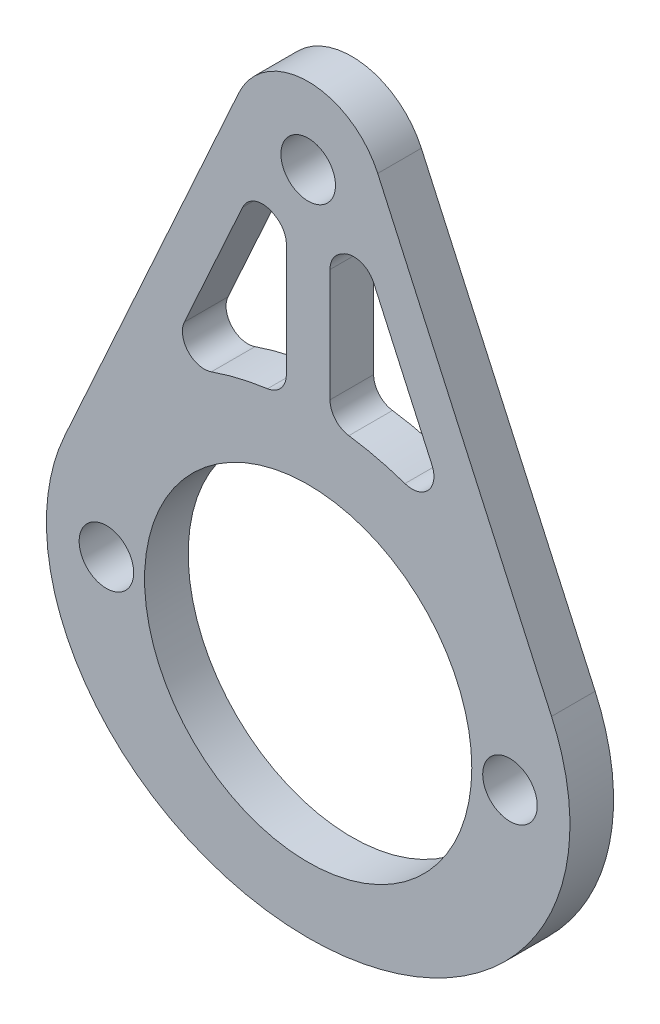
SolidWorks part; units mm, degrees
material "2018 合金"
ref_plane "正面" through (0, 0, 0) normal (0, 0, 1) x (1, 0, 0)
ref_plane "平面" through (0, 0, 0) normal (0, 1, 0) x (1, 0, 0)
ref_plane "右側面" through (0, 0, 0) normal (1, 0, 0) x (0, 0, -1)
sketch "ｽｹｯﾁ1" plane through (0, 0, 0) normal (0, 0, 1) x (1, 0, 0)
  line L0 (0, 0) -> (9.25, 0) construction
  line L1 (0, 0) -> (0, 7.5) construction
  line L2 (0, 0) -> (0, 20) construction
  line L3 (-11.1545, 3.8716) -> (-3.1877, 21.4451)
  line L4 (11.1545, 3.8716) -> (3.1877, 21.4451)
  circle A0 centre (0, 0) radius 7.5
  circle A1 centre (9.25, 0) radius 2.75 construction
  circle A2 centre (9.25, 0) radius 1
  circle A3 centre (0, 0) radius 10.5 construction
  circle A4 centre (-9.25, 0) radius 1
  circle A5 centre (0, 20) radius 3 construction
  arc A6 (3.1877, 21.4451) -> (-3.1877, 21.4451) centre (0, 20) ccw
  ellipse E0 centre (0, 0) end of major axis (12, 0) minor radius 10.5 (-11.1545, 3.8716) -> (11.1545, 3.8716) ccw
  dimension "D1" = 18.5
  dimension "D2" = 15
  dimension "D3" = 5.5
  dimension "D4" = 2
  dimension "D7" = 6
  dimension "D8" = 0.5
  dimension "D6" = 20
  dimension "D5" = 3
extrude "ﾎﾞｽ - 押し出し1" add sketch "ｽｹｯﾁ1" along normal blind 2
hole_wizard "M3 ねじ穴1" positions "ｽｹｯﾁ2" profile "ｽｹｯﾁ3" tap size "M3" standard "JIS" end condition through all
sketch "ｽｹｯﾁ2" plane through (0, 0, 0) normal (0, 0, -1) x (-1, 0, 0)
  point P0 (-9.25, 0)
  point P3 (9.25, 0)
sketch "ｽｹｯﾁ3" plane through (9.25, 0, 0) normal (1, 0, 0) x (0, 1, 0)
  line L0 (0, 0) -> (0, 2)
  line L1 (0, 2) -> (1.25, 2)
  line L2 (1.25, 2) -> (1.25, 0)
  line L5 (1.25, 0) -> (0, 0)
  line L11 (0, -6.35) -> (0, 107.95) construction
  dimension "次ｻｰﾌｪｽまでのねじ下穴ﾄﾞﾘﾙ直径" = 2.5
  dimension "次ｻｰﾌｪｽまでのねじ下穴ﾄﾞﾘﾙの深さ" = 2
cosmetic thread "穴のねじ山1" parameters "D2"=3
cosmetic thread "穴のねじ山2" parameters "D2"=3
sketch "ｽｹｯﾁ4" plane through (0, 0, 0) normal (0, 0, -1) x (-1, 0, 0)
  line L0 (0, 20) -> (0, 0) construction
  line L2 (1, 10.4635) -> (-1, 10.4635)
  line L3 (1, 10.4635) -> (1, 17.1716)
  line L4 (1, 17.1716) -> (-1, 17.1716)
  line L5 (-1, 10.4635) -> (-1, 17.1716)
  line L6 (1, 10.4635) -> (-1, 17.1716) construction
  line L7 (1, 17.1716) -> (-1, 10.4635) construction
  line L9 (1.3662, 20.6193) -> (9.3329, 3.0458)
  line L10 (1.3662, 20.6193) -> (9.3329, 3.0458)
  line L12 (-9.3329, 3.0458) -> (-1.3662, 20.6193)
  line L13 (-9.3329, 3.0458) -> (-1.3662, 20.6193)
  circle A2 centre (0, 20) radius 3
  ellipse E0 centre (0, 0) end of major axis (-12, 0) minor radius 10.5 (8.5484, -7.369) -> (-8.5484, -7.369) ccw construction
  ellipse E1 centre (0, 0) end of major axis (-12, 0) minor radius 10.5 (8.5484, -7.369) -> (-8.5484, -7.369) ccw
  point P5 (0, 20)
  point P18 (0, 13.8175)
  point P23 (-1.1056, 10.4553)
  dimension "D4" = 6
  dimension "D1" = 2
  dimension "D2" = 2
  dimension "D3" = 2
extrude "ｶｯﾄ - 押し出し1" cut sketch "ｽｹｯﾁ4" against normal through all contours E1 L5 A2 L13 | E1 L10 A2 L3 region at (-3.0466, 13.0793, 0) region at (3.0466, 13.0793, 0)
fillet "ﾌｨﾚｯﾄ1" radius 1 8 edges at (-1, 17.1716, 1) (-2.4389, 18.2531, 1) (-6.7885, 8.6583, 1) (2.4389, 18.2531, 1) (1, 17.1716, 1) (1, 10.4635, 1) (6.7885, 8.6583, 1) (-1, 10.4635, 1)
hole_wizard "M3 ねじ穴2" positions "ｽｹｯﾁ5" profile "ｽｹｯﾁ6" tap size "M3" standard "JIS" end condition through all
sketch "ｽｹｯﾁ5" plane through (0, 0, 2) normal (0, 0, 1) x (1, 0, 0)
  point P0 (0, 20)
sketch "ｽｹｯﾁ6" plane through (0, 20, 2) normal (1, 0, 0) x (0, -1, 0)
  line L0 (0, 0) -> (0, 2)
  line L1 (0, 2) -> (1.25, 2)
  line L2 (1.25, 2) -> (1.25, 0)
  line L5 (1.25, 0) -> (0, 0)
  line L11 (0, -6.35) -> (0, 107.95) construction
  dimension "次ｻｰﾌｪｽまでのねじ下穴ﾄﾞﾘﾙ直径" = 2.5
  dimension "次ｻｰﾌｪｽまでのねじ下穴ﾄﾞﾘﾙの深さ" = 2
cosmetic thread "穴のねじ山3" parameters "D2"=3
